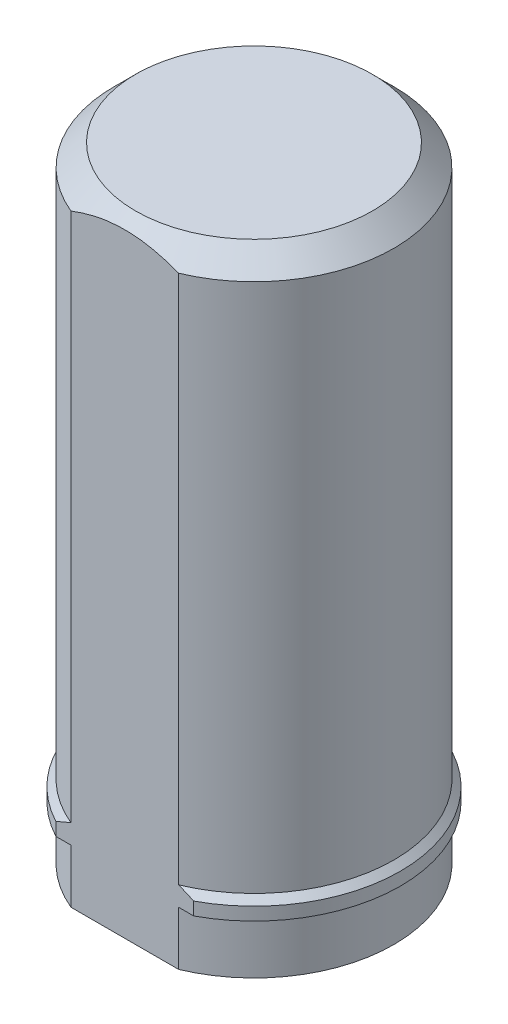
SolidWorks part; units mm, degrees
ref_plane "Top Plane" through (0, 0, 0) normal (0, 0, 1) x (1, 0, 0)
ref_plane "Right Plane" through (0, 0, 0) normal (0, 1, 0) x (1, 0, 0)
ref_plane "Front Plane" through (0, 0, 0) normal (1, 0, 0) x (0, 0, -1)
sketch "Sketch1" plane through (0, 0, 0) normal (0, 1, 0) x (1, 0, 0)
  line L0 (-1.25, -3) -> (1.25, -3)
  arc A0 (1.25, -3) -> (-1.25, -3) centre (0, 0) ccw
  dimension "D1" = 6.5
  dimension "D2" = 2.5
extrude "Boss-Extrude1" add sketch "Sketch1" along normal mid plane 14.5
sketch "Sketch2" plane through (0, -7.25, 0) normal (0, -1, 0) x (1, 0, 0)
  line L0 (-1.25, 3) -> (-1.6, 3)
  line L1 (1.25, 3) -> (1.6, 3)
  arc A1 (-1.25, 3) -> (1.25, 3) centre (0, 0) ccw construction
  arc A2 (-1.3077, 3.1385) -> (1.3077, 3.1385) centre (0, 0) ccw
  arc A3 (-1.6, 3) -> (1.6, 3) centre (0, 0) ccw
  arc A4 (-1.25, 3) -> (1.25, 3) centre (0, 0) ccw
  dimension "D1" = 0.15
extrude "Boss-Extrude2" add sketch "Sketch2" against normal blind 0.5 from offset 1.25 offset against normal yes
chamfer "Chamfer1" distance 0.2 angle 45 1 edges at (0, -5.5, -3.4)
chamfer "Chamfer2" distance 0.5 angle 45 1 edges at (0, 7.25, -3.25)
